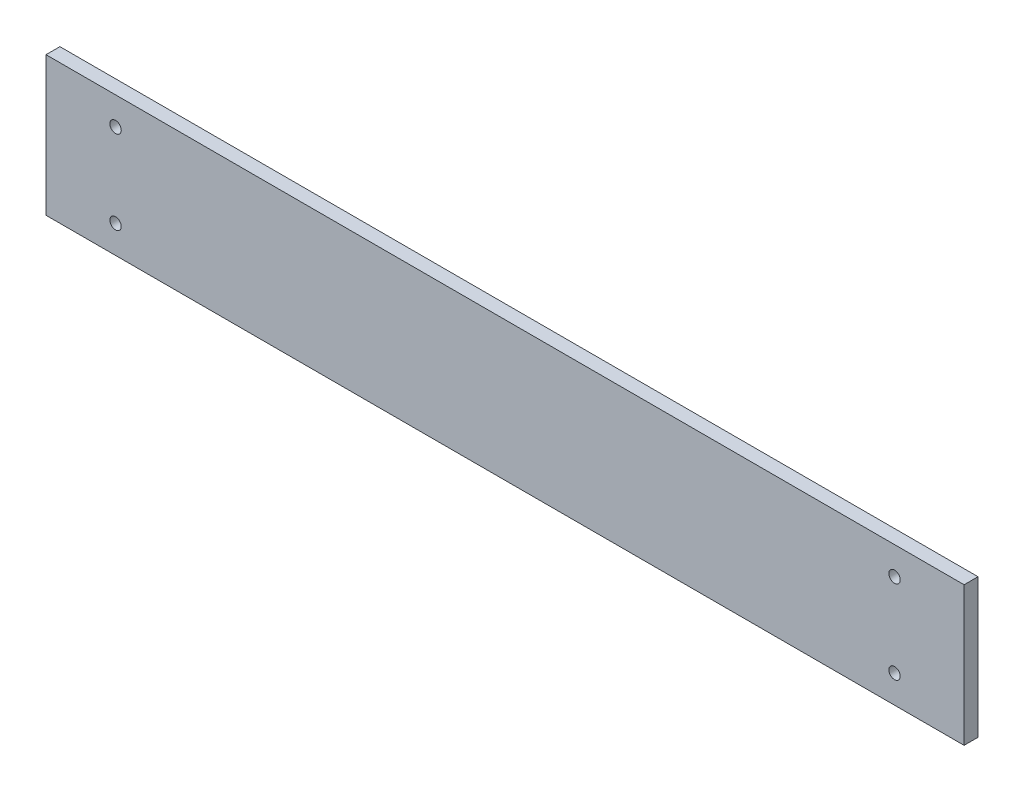
SolidWorks part; units mm, degrees
ref_plane "Plan de face" through (0, 0, 0) normal (0, 0, 1) x (1, 0, 0)
ref_plane "Plan de dessus" through (0, 0, 0) normal (0, 1, 0) x (1, 0, 0)
ref_plane "Plan de droite" through (0, 0, 0) normal (1, 0, 0) x (0, 0, -1)
sketch "Esquisse2" plane through (0, 0, 0) normal (0, 0, 1) x (1, 0, 0)
  line L0 (0, 89.4193) -> (0, -90.234) construction
  line L1 (-170, -25) -> (170, -25) construction
  line L2 (-170, -25) -> (-170, 25) construction
  line L3 (-170, 25) -> (170, 25) construction
  line L4 (170, -25) -> (170, 25) construction
  line L5 (-170, -25) -> (170, 25) construction
  line L6 (-170, 25) -> (170, -25) construction
  line L12 (165, -25) -> (-165, -25)
  line L13 (165, -25) -> (165, 25)
  line L14 (165, 25) -> (-165, 25)
  line L15 (-165, -25) -> (-165, 25)
  line L16 (165, -25) -> (-165, 25) construction
  line L17 (165, 25) -> (-165, -25) construction
  circle A0 centre (-140, 15) radius 2.05
  circle A1 centre (140, 15) radius 2.05
  circle A2 centre (-140, -15) radius 2.05
  circle A3 centre (140, -15) radius 2.05
  point P0 (0, 0)
  point P5 (0, 0)
  point P6 (0, 0)
  dimension "D4" = 4.1
  dimension "D8" = 10
  dimension "D1" = 340
  dimension "D2" = 50
  dimension "D3" = 5
  dimension "D5" = 0
  dimension "D6" = 25
  dimension "D7" = 10
  dimension "D9" = 140
extrude "Boss.-Extru.1" add sketch "Esquisse2" along normal blind 5
